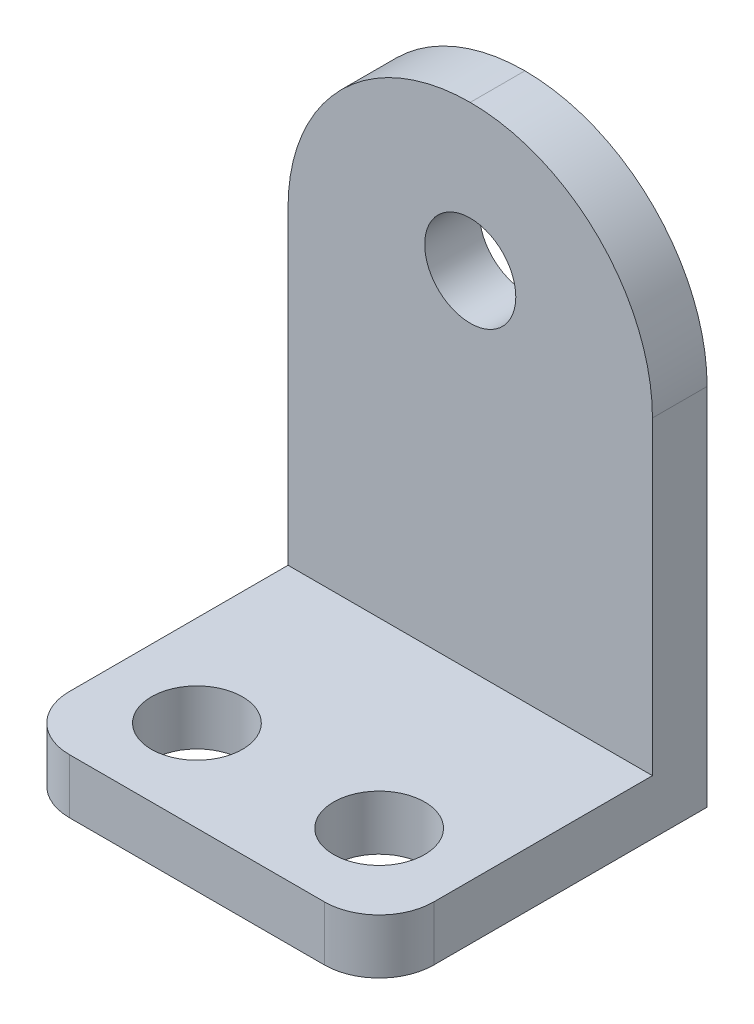
SolidWorks part; units mm, degrees
ref_plane "Front Plane" through (0, 0, 0) normal (0, 0, 1) x (1, 0, 0)
ref_plane "Top Plane" through (0, 0, 0) normal (0, 1, 0) x (1, 0, 0)
ref_plane "Right Plane" through (0, 0, 0) normal (1, 0, 0) x (0, 0, -1)
sketch "Sketch3" plane through (0, 0, 0) normal (1, 0, 0) x (0, 0, -1)
  line L0 (0, 0) -> (0, 30)
  line L1 (0, 30) -> (-3, 30)
  line L2 (-3, 30) -> (-3, 3)
  line L3 (-3, 3) -> (-18, 3)
  line L4 (-18, 3) -> (-18, 0)
  line L5 (-18, 0) -> (0, 0)
  dimension "D1" = 3
  dimension "D2" = 3
  dimension "D3" = 30
  dimension "D4" = 18
extrude "Boss-Extrude3" add sketch "Sketch3" along normal blind 20
sketch "Sketch4" plane through (0, 0, 3) normal (0, 0, 1) x (1, 0, 0)
  line L0 (20, 30) -> (0, 30) construction
  line L1 (0, 30) -> (0, 3) construction
  circle A0 centre (10, 22) radius 2.5
  point P4 (0, 0)
  dimension "D1" = 8
  dimension "D3" = 5
  dimension "D2" = 10
extrude "Cut-Extrude1" cut sketch "Sketch4" against normal blind 20
sketch "Sketch5" plane through (0, 3, 0) normal (0, 1, 0) x (1, 0, 0)
  line L0 (0, -3) -> (0, -18) construction
  line L1 (20, -3) -> (20, -18) construction
  line L2 (20, -18) -> (0, -18) construction
  circle A0 centre (5, -13) radius 2.5
  circle A1 centre (15, -13) radius 2.5
  dimension "D1" = 5
  dimension "D2" = 5
  dimension "D3" = 5
  dimension "D4" = 5
  dimension "D5" = 5
extrude "Cut-Extrude2" cut sketch "Sketch5" against normal blind 20
fillet "Fillet1" radius 10 2 edges at (0, 30, 1.5) (20, 30, 1.5)
fillet "Fillet2" radius 3 2 edges at (0, 1.5, 18) (20, 1.5, 18)
